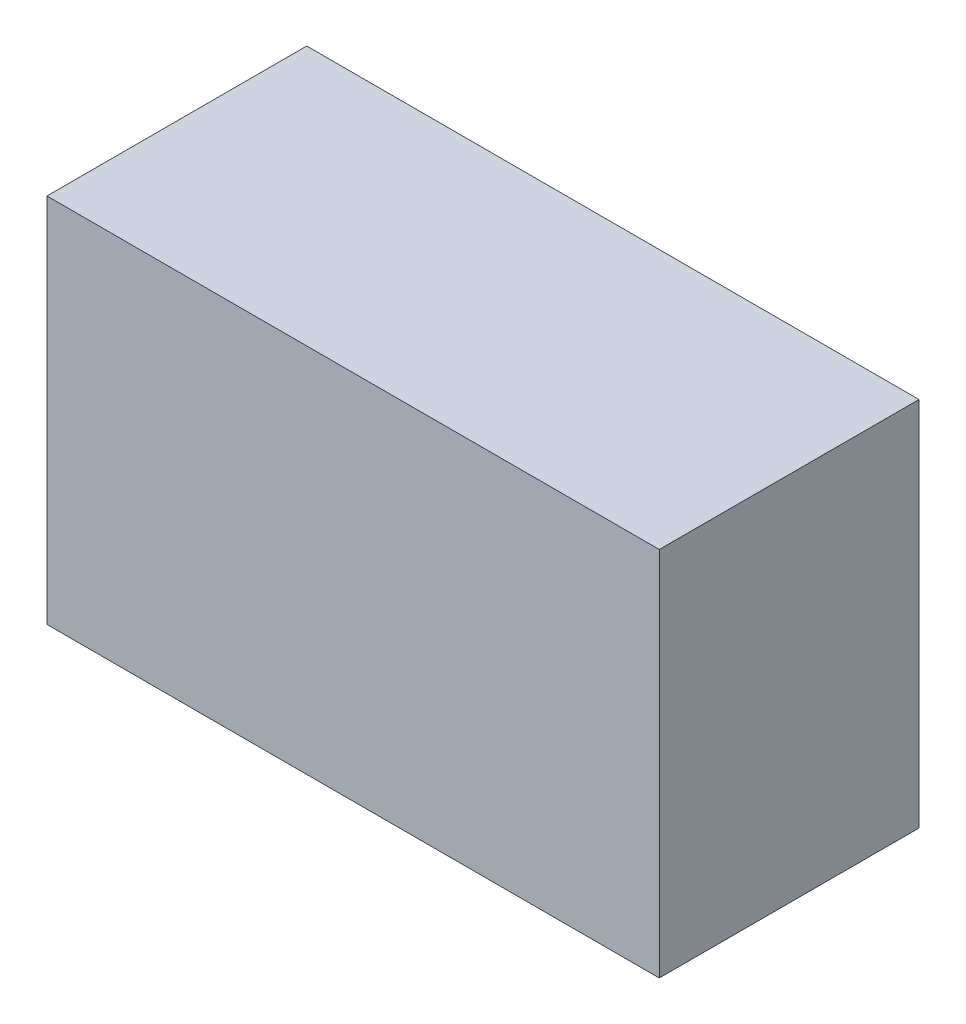
SolidWorks part; units mm, degrees
ref_plane "Ebene vorne" through (0, 0, 0) normal (0, 0, 1) x (1, 0, 0)
ref_plane "Ebene oben" through (0, 0, 0) normal (0, 1, 0) x (1, 0, 0)
ref_plane "Ebene rechts" through (0, 0, 0) normal (1, 0, 0) x (0, 0, -1)
sketch "Sketch1" plane through (0, 0, 0) normal (0, 0, 1) x (1, 0, 0)
  line L0 (0, 0) -> (0, 20.4208) construction
  line L1 (-16.5, 10) -> (16.5, 10)
  line L2 (-16.5, 10) -> (-16.5, -10)
  line L3 (-16.5, -10) -> (16.5, -10)
  line L4 (16.5, 10) -> (16.5, -10)
  line L5 (0, 0) -> (42.3663, 0) construction
  dimension "D1" = 33
  dimension "D2" = 20
extrude "Boss-Extrude1" add sketch "Sketch1" along normal blind 14
